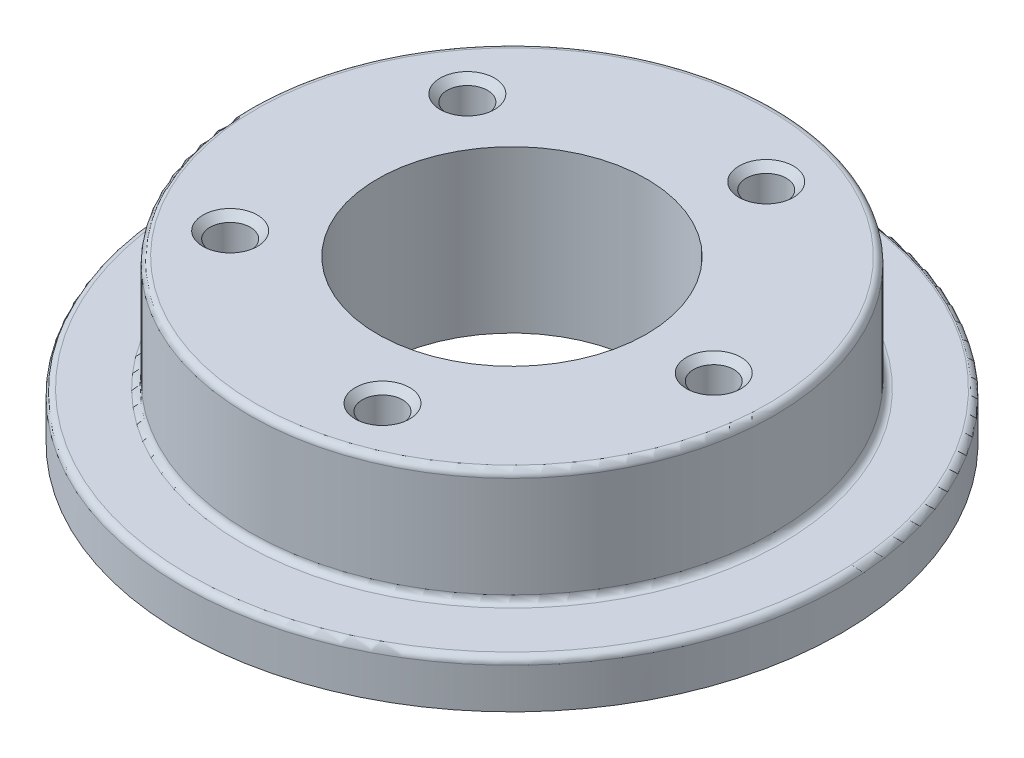
SolidWorks part; units mm, degrees
ref_plane "Front" through (0, 0, 0) normal (0, 0, 1) x (1, 0, 0)
ref_plane "Top" through (0, 0, 0) normal (0, 1, 0) x (1, 0, 0)
ref_plane "Right" through (0, 0, 0) normal (1, 0, 0) x (0, 0, -1)
sketch "Sketch1" plane through (0, 0, 0) normal (0, 1, 0) x (1, 0, 0)
  circle A0 centre (0, 0) radius 24.5
  circle A1 centre (0, 0) radius 19.5
  circle A2 centre (0, 0) radius 10
  dimension "D1" = 49
  dimension "D2" = 39
  dimension "D3" = 20
extrude "Extrude1" add sketch "Sketch1" along normal blind 3.5 contours A0 | A2
extrude "Extrude2" add sketch "Sketch1<3>" along normal blind 12 contours A1 | A2
sketch "Sketch1<3>" plane through (0, 0, 0) normal (0, 1, 0) x (1, 0, 0) same geometry as "Sketch1"
hole_wizard "Ø3.0 Diameter Hole1" positions "3DSketch1" profile "Sketch3" hole size "Ø3.0" standard "Ansi Metric"
sketch3d "3DSketch1"
  line L4 (0, 12, 0) -> (15, 12, 0) construction
  line L5 (0, 12, 0) -> (0, 3.5, 0) construction
  point P6 (15, 12, 0)
  dimension "D1" = 15
sketch "Sketch3" plane through (15, 12, 0) normal (1, 0, 0) x (0, 0, 1)
  line L0 (0, 0) -> (0, 10.9013)
  line L1 (0, 10.9013) -> (1.5, 10)
  line L2 (1.5, 10) -> (1.5, 0.525)
  line L3 (1.5, 0.525) -> (2.025, 0)
  line L5 (2.025, 0) -> (0, 0)
  line L6 (-1.5, 0.525) -> (-2.025, 0) construction
  line L10 (0, 10.9013) -> (-1.5, 10) construction
  line L11 (0, -6.35) -> (0, 107.95) construction
  dimension "Hole Dia." = 3
  dimension "Hole Depth" = 10
  dimension "Near C'Sink Dia." = 4.05
  dimension "Near C'Sink Angle" = 90
  dimension "Drill Angle" = 118
pattern_circular "CirPattern1" count 5 over 360 about axis through (0, 12, 0) along (0, -1, 0) of "Ø3.0 Diameter Hole1"
fillet "Finishing Fillet" radius 0.5 3 edges at (19.5, 12, 0) (0, 3.5, 19.5) (24.5, 3.5, 0)
